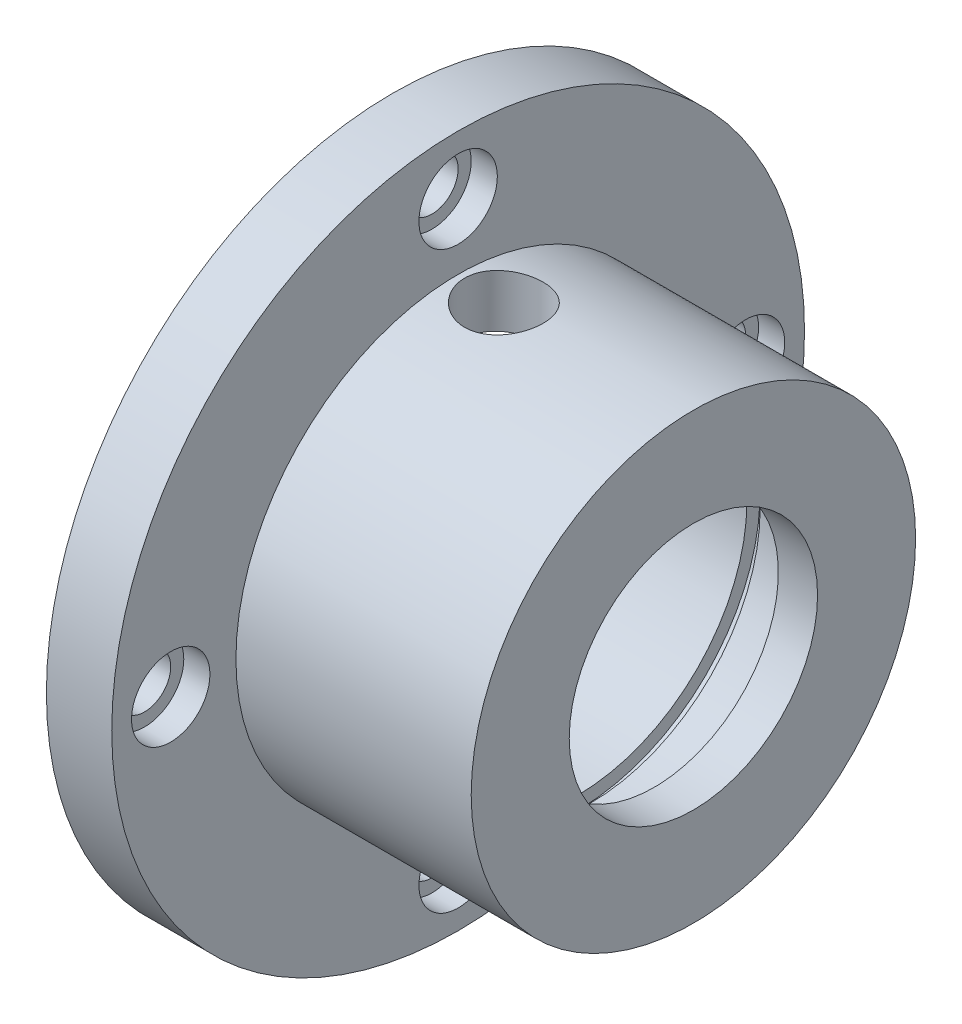
SolidWorks part; units mm, degrees
ref_plane "Front Plane" through (0, 0, 0) normal (0, 0, 1) x (1, 0, 0)
ref_plane "Top Plane" through (0, 0, 0) normal (0, 1, 0) x (1, 0, 0)
ref_plane "Right Plane" through (0, 0, 0) normal (1, 0, 0) x (0, 0, -1)
sketch "Sketch1" plane through (0, 0, 0) normal (1, 0, 0) x (0, 0, -1)
  circle A0 centre (0, 0) radius 26.5
  circle A2 centre (0, -21.9877) radius 2
  circle A3 centre (-21.9877, 0) radius 2
  circle A4 centre (0, 21.9877) radius 2
  circle A5 centre (21.9877, 0) radius 2
  point P14 (0, 0)
  dimension "D1" = 53
  dimension "D2" = 4
  dimension "D3" = 4
extrude "Boss-Extrude1" add sketch "Sketch1" along normal mid plane 23
sketch "Sketch2" plane through (11.5, 0, 0) normal (1, 0, 0) x (0, 0, -1)
  circle A0 centre (0, 0) radius 17
  circle A1 centre (0, 0) radius 26.5
  circle M3 centre (0, 21.9877) radius 2
  circle M4 centre (0, -21.9877) radius 2
  circle M5 centre (0, 0) radius 26.5
  circle M6 centre (-21.9877, 0) radius 2
  circle M7 centre (21.9877, 0) radius 2
  dimension "D1" = 53
  dimension "D3" = 34
extrude "Cut-Extrude1" cut sketch "Sketch2" against normal blind 18 contours A0 M5 M4 M6 M7 M3 region at (11.5, 0, 25.7505)
sketch "Sketch3" plane through (-11.5, 0, 0) normal (-1, 0, 0) x (0, 0, 1)
  circle A0 centre (0, 0) radius 13
  dimension "D1" = 26
extrude "Cut-Extrude2" cut sketch "Sketch3" against normal blind 20
sketch "Sketch4" plane through (8.5, 0, 0) normal (-1, 0, 0) x (0, 0, 1)
  circle A0 centre (0, 0) radius 9.5
  dimension "D1" = 19
extrude "Cut-Extrude3" cut sketch "Sketch4" against normal blind 20
ref_plane "Plane1" through (3.1, 0, 0) normal (-1, 0, 0) x (0, 0, 1)
sketch "Sketch5" plane through (3.1, 0, 0) normal (-1, 0, 0) x (0, 0, 1)
  circle A0 centre (0, 0) radius 14
  dimension "D1" = 28
extrude "Cut-Extrude4" cut sketch "Sketch5" against normal mid plane 1.01
ref_axis "Axis1" through (26.7383, 0, 0) along (-1, 0, 0)
sketch "Sketch6" plane through (0, 0, 0) normal (0, 1, 0) x (1, 0, 0)
  line L0 (26.7383, 0) -> (-32.37, 0) construction
  line L1 (11.5, -17) -> (11.5, 17) construction
  circle A0 centre (-3, 0) radius 3
  dimension "D1" = 14.5
extrude "Cut-Extrude5" cut sketch "Sketch6" along normal blind 33
ref_plane "Plane3" through (0, 17, 0) normal (0, 1, 0) x (1, 0, 0)
sketch "Sketch8" plane through (0, 17, 0) normal (0, 1, 0) x (1, 0, 0)
  line L1 (0.1411, -6) -> (-6.1411, -6)
  line L2 (0.1411, -6) -> (0.1411, 6)
  line L3 (0.1411, 6) -> (-6.1411, 6)
  line L4 (-6.1411, -6) -> (-6.1411, 6)
  line L5 (0.1411, -6) -> (-6.1411, 6) construction
  line L6 (0.1411, 6) -> (-6.1411, -6) construction
  point P0 (-3, 0)
  dimension "D1" = 12
extrude "Cut-Extrude6" [suppressed] cut sketch "Sketch8" against normal blind 1
sketch "Sketch9" plane through (-6.5, 0, 0) normal (1, 0, 0) x (0, 0, -1)
  circle A0 centre (0, 21.9877) radius 3
  circle A1 centre (21.9877, 0) radius 3
  circle A2 centre (0, -21.9877) radius 3
  circle A3 centre (-21.9877, 0) radius 3
  point P12 (0, 0)
  dimension "D1" = 4
extrude "Cut-Extrude7" cut sketch "Sketch9" against normal blind 2
